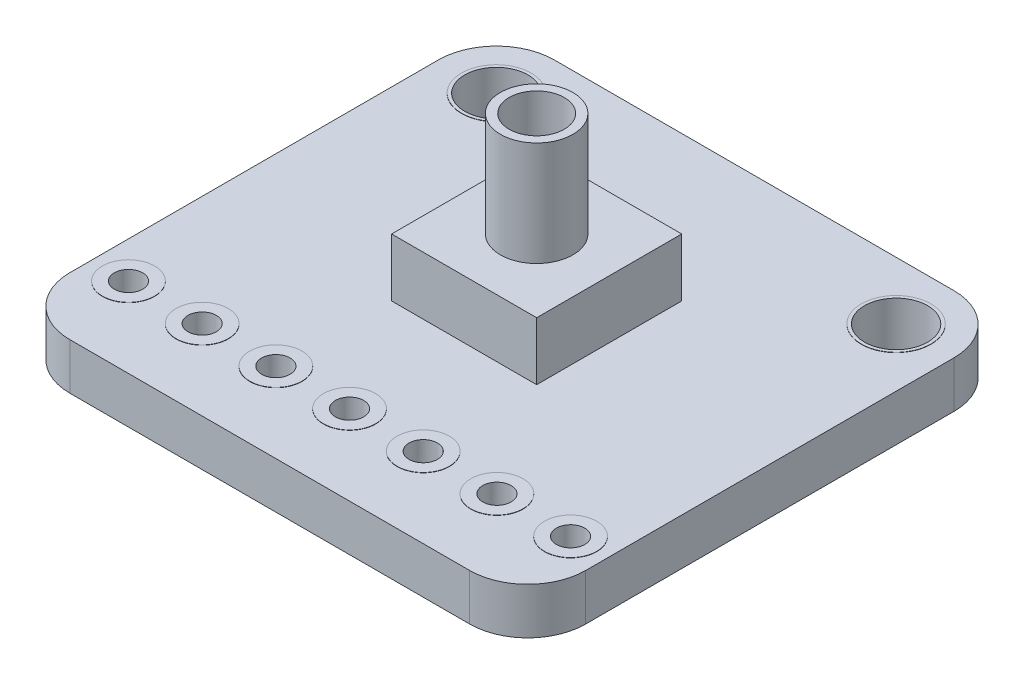
SolidWorks part; units mm, degrees
ref_plane "Front Plane" through (0, 0, 0) normal (0, 0, 1) x (1, 0, 0)
ref_plane "Top Plane" through (0, 0, 0) normal (0, 1, 0) x (1, 0, 0)
ref_plane "Right Plane" through (0, 0, 0) normal (1, 0, 0) x (0, 0, -1)
sketch "Sketch1" plane through (0, 0, 0) normal (0, 1, 0) x (1, 0, 0)
  line L1 (-6.89, 8.35) -> (6.89, 8.35)
  line L2 (-8.89, 6.35) -> (-8.89, -6.35)
  line L3 (-6.89, -8.35) -> (6.89, -8.35)
  line L4 (8.89, 6.35) -> (8.89, -6.35)
  line L5 (-8.89, 8.35) -> (8.89, -8.35) construction
  line L6 (-8.89, -8.35) -> (8.89, 8.35) construction
  arc A0 (-8.89, -6.35) -> (-6.89, -8.35) centre (-6.89, -6.35) ccw
  arc A1 (6.89, -8.35) -> (8.89, -6.35) centre (6.89, -6.35) ccw
  arc A2 (6.89, 8.35) -> (8.89, 6.35) centre (6.89, 6.35) cw
  arc A3 (-6.89, 8.35) -> (-8.89, 6.35) centre (-6.89, 6.35) ccw
  point P0 (0, 0)
  dimension "D3" = 2
  dimension "D1" = 17.78
  dimension "D2" = 16.7
extrude "Boss-Extrude1" add sketch "Sketch1" along normal blind 1.6
sketch "Sketch2" plane through (0, 1.6, 0) normal (0, 1, 0) x (1, 0, 0)
  line L0 (0, 0) -> (0, 8.35) construction
  line L1 (-8.89, -8.35) -> (8.89, 8.35) construction
  line L2 (-6.89, 8.35) -> (6.89, 8.35) construction
  line L3 (-6.89, -8.35) -> (6.89, -8.35) construction
  line L4 (-8.89, -4.33) -> (8.89, -4.33) construction
  line L5 (-8.89, -4.33) -> (-8.89, -6.87) construction
  line L6 (-8.89, -6.87) -> (8.89, -6.87) construction
  line L7 (8.89, -4.33) -> (8.89, -6.87) construction
  line L8 (-8.89, -4.33) -> (8.89, -6.87) construction
  line L9 (-8.89, -6.87) -> (8.89, -4.33) construction
  line L10 (-8.89, 6.35) -> (-8.89, -6.35) construction
  line L11 (8.89, 6.35) -> (8.89, -6.35) construction
  circle A0 centre (-6.89, 6.35) radius 1.1
  circle A1 centre (6.89, 6.35) radius 1.1
  circle A2 centre (-7.62, -5.6) radius 0.5
  circle A3 centre (-5.08, -5.6) radius 0.5
  circle A4 centre (-2.54, -5.6) radius 0.5
  circle A5 centre (0, -5.6) radius 0.5
  circle A6 centre (2.54, -5.6) radius 0.5
  circle A7 centre (5.08, -5.6) radius 0.5
  circle A8 centre (7.62, -5.6) radius 0.5
  point P2 (-6.89, 6.35)
  point P12 (0, -5.6)
  point P22 (-8.89, -5.6)
  dimension "D1" = 2.2
  dimension "D5" = 1
  dimension "D2" = 2.75
  dimension "D3" = 2.54
  dimension "D4" = 1.27
  dimension "D7" = 2.54
  dimension "D6" = 7
extrude "Cut-Extrude1" cut sketch "Sketch2" against normal blind 1.6
ref_plane "Plane1" through (0, 1.61, 0) normal (0, 1, 0) x (1, 0, 0)
sketch "Sketch3" plane through (0, 1.61, 0) normal (0, 1, 0) x (1, 0, 0)
  circle A0 centre (-6.89, 6.35) radius 1.1 construction
  circle A1 centre (-6.89, 6.35) radius 1.1 construction
  circle A2 centre (6.89, 6.35) radius 1.1 construction
  circle A3 centre (6.89, 6.35) radius 1.1 construction
  circle A4 centre (-6.89, 6.35) radius 1.2
  circle A5 centre (6.89, 6.35) radius 1.2
  circle A6 centre (-6.89, 6.35) radius 1.09
  circle A7 centre (6.89, 6.35) radius 1.09
  circle A8 centre (7.62, -5.6) radius 0.5 construction
  circle A9 centre (5.08, -5.6) radius 0.5 construction
  circle A10 centre (2.54, -5.6) radius 0.5 construction
  circle A11 centre (0, -5.6) radius 0.5 construction
  circle A12 centre (-2.54, -5.6) radius 0.5 construction
  circle A13 centre (-5.08, -5.6) radius 0.5 construction
  circle A14 centre (-7.62, -5.6) radius 0.5 construction
  circle A15 centre (7.62, -5.6) radius 0.5 construction
  circle A16 centre (5.08, -5.6) radius 0.5 construction
  circle A17 centre (2.54, -5.6) radius 0.5 construction
  circle A18 centre (0, -5.6) radius 0.5 construction
  circle A19 centre (-2.54, -5.6) radius 0.5 construction
  circle A20 centre (-5.08, -5.6) radius 0.5 construction
  circle A21 centre (-7.62, -5.6) radius 0.5 construction
  circle A22 centre (7.62, -5.6) radius 0.9
  circle A23 centre (5.08, -5.6) radius 0.9
  circle A24 centre (2.54, -5.6) radius 0.9
  circle A25 centre (0, -5.6) radius 0.9
  circle A26 centre (-2.54, -5.6) radius 0.9
  circle A27 centre (-5.08, -5.6) radius 0.9
  circle A28 centre (-7.62, -5.6) radius 0.9
  circle A29 centre (7.62, -5.6) radius 0.49
  circle A30 centre (5.08, -5.6) radius 0.49
  circle A31 centre (2.54, -5.6) radius 0.49
  circle A32 centre (0, -5.6) radius 0.49
  circle A33 centre (-2.54, -5.6) radius 0.49
  circle A34 centre (-5.08, -5.6) radius 0.49
  circle A35 centre (-7.62, -5.6) radius 0.49
  dimension "D1" = 0.1
  dimension "D2" = 0.01
  dimension "D3" = 0.4
  dimension "D4" = 0.01
extrude "Boss-Extrude2" add sketch "Sketch3" against normal offset from surface (1.62 mm away) 0.01 up to face at (-2.54, 0, 6.1) offset beyond the face yes
sketch "Sketch5" plane through (0, 1.6, 0) normal (0, 1, 0) x (1, 0, 0)
  line L0 (-6.89, 8.35) -> (6.89, 8.35) construction
  line L1 (-2.5, 3.35) -> (2.5, 3.35)
  line L2 (-2.5, 3.35) -> (-2.5, -1.65)
  line L3 (-2.5, -1.65) -> (2.5, -1.65)
  line L4 (2.5, 3.35) -> (2.5, -1.65)
  line L5 (-2.5, 3.35) -> (2.5, -1.65) construction
  line L6 (-2.5, -1.65) -> (2.5, 3.35) construction
  point P0 (0, 0.85)
  dimension "D1" = 5
  dimension "D2" = 5
extrude "Boss-Extrude3" add sketch "Sketch5" along normal blind 2
sketch "Sketch6" plane through (0, 3.6, 0) normal (0, 1, 0) x (1, 0, 0)
  line L0 (-2.5, 3.35) -> (2.5, -1.65) construction
  circle A0 centre (0, 0.85) radius 1.25
  circle A2 centre (0, 0.85) radius 0.95
  dimension "D1" = 2.5
  dimension "D2" = 0.3
extrude "Boss-Extrude4" add sketch "Sketch6" along normal blind 3.6
